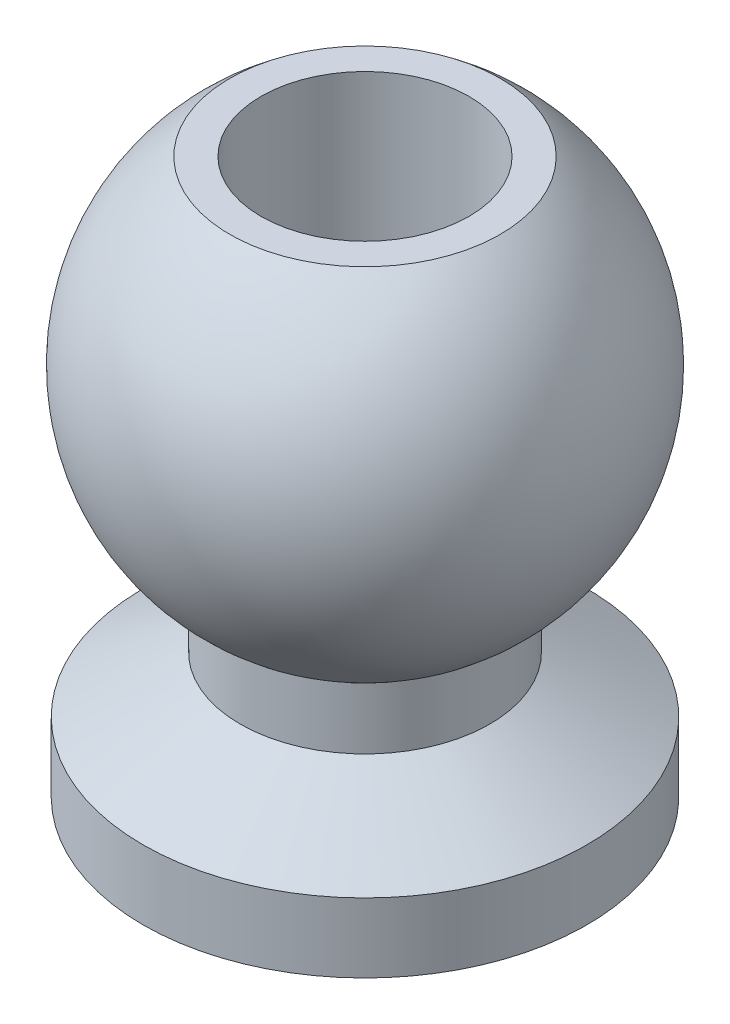
SolidWorks part; units mm, degrees
ref_plane "前视" through (0, 0, 0) normal (0, 0, 1) x (1, 0, 0)
ref_plane "上视" through (0, 0, 0) normal (0, 1, 0) x (1, 0, 0)
ref_plane "右视" through (0, 0, 0) normal (1, 0, 0) x (0, 0, -1)
sketch "Sketch1" plane through (0, 0, 0) normal (1, 0, 0) x (0, 0, -1)
  line L0 (0, 8.65) -> (0, 0)
  line L1 (0, 0) -> (3.2, 0)
  line L2 (3.2, 0) -> (3.2, 1)
  line L3 (3.2, 1) -> (1.8, 1.8083)
  line L4 (1.8, 1.8083) -> (1.8, 2.694)
  arc A0 (1.8, 2.694) -> (0, 8.65) centre (0, 5.4) ccw
  dimension "D1" = 3.25
  dimension "D2" = 1
  dimension "D3" = 30
  dimension "D4" = 1.8
  dimension "D5" = 3.2
  dimension "D6" = 5.4
revolve "Revolve1" add sketch "Sketch1" angle 360 about L0
sketch "Sketch2" plane through (0, 0, 0) normal (0, -1, 0) x (1, 0, 0)
  circle A0 centre (0, 0) radius 1.5
  dimension "D1" = 3
extrude "Cut-Extrude1" cut sketch "Sketch2" against normal blind 10
sketch "Sketch3" plane through (0, 0, 0) normal (1, 0, 0) x (0, 0, -1)
  line L1 (-3.2147, 9.0598) -> (8.2567, 9.0598)
  line L2 (-3.2147, 9.0598) -> (-3.2147, 8)
  line L3 (-3.2147, 8) -> (8.2567, 8)
  line L4 (8.2567, 9.0598) -> (8.2567, 8)
  dimension "D1" = 8
extrude "Cut-Extrude2" cut sketch "Sketch3" against normal blind 10 and the other way blind 10 contours L3 L4 L1 L2
